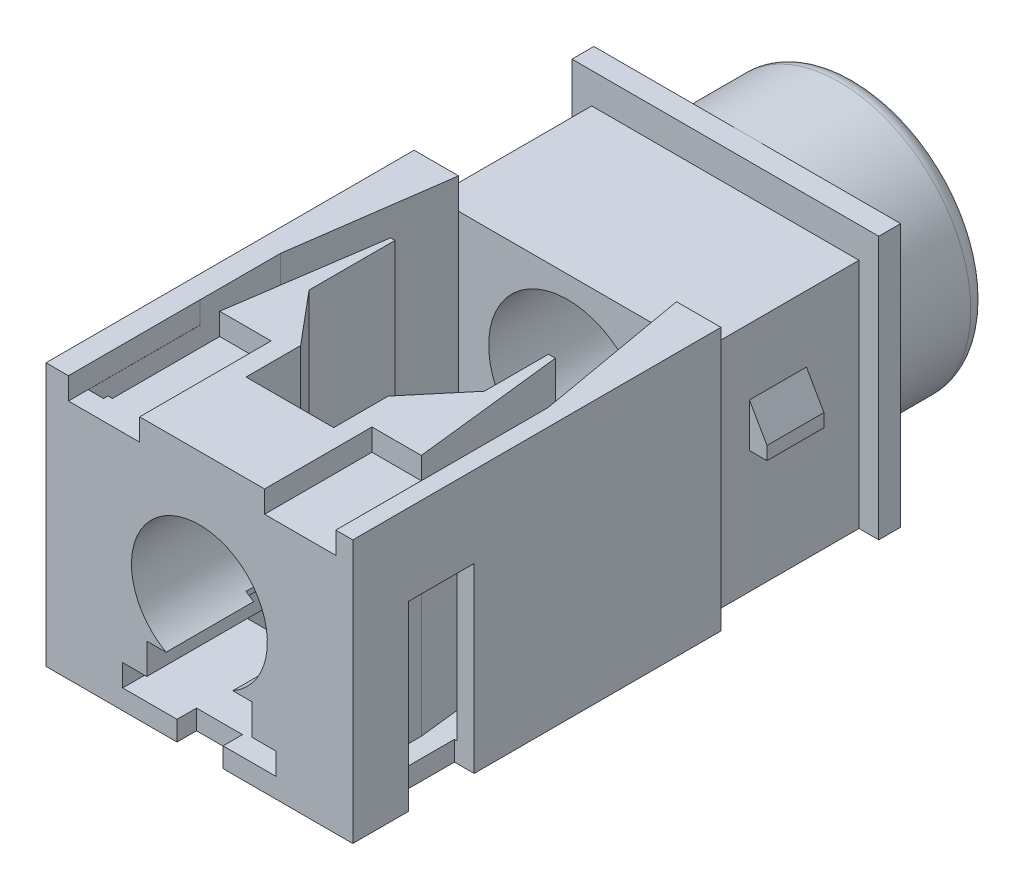
SolidWorks part; units mm, degrees
ref_plane "Front Plane" through (0, 0, 0) normal (0, 0, 1) x (1, 0, 0)
ref_plane "Top Plane" through (0, 0, 0) normal (0, 1, 0) x (1, 0, 0)
ref_plane "Right Plane" through (0, 0, 0) normal (1, 0, 0) x (0, 0, -1)
sketch "Szkic1" plane through (0, 0, 0) normal (0, 0, 1) x (1, 0, 0)
  circle A0 centre (0, 0) radius 3
  circle A1 centre (0, 0) radius 1.8
  dimension "D1" = 6
  dimension "D2" = 3.6
extrude "Dodanie-wyciągnięcie1" add sketch "Szkic1" along normal blind 2.5
sketch "Szkic2" plane through (0, 0, 2.5) normal (0, 0, 1) x (1, 0, 0)
  line L5 (3.5, -3) -> (-3.5, -3)
  line L6 (3.5, -3) -> (3.5, 3)
  line L7 (3.5, 3) -> (-3.5, 3)
  line L8 (-3.5, -3) -> (-3.5, 3)
  line L9 (3.5, -3) -> (-3.5, 3) construction
  line L10 (3.5, 3) -> (-3.5, -3) construction
  circle A2 centre (0, 0) radius 1.8 construction
  circle A3 centre (0, 0) radius 1.8
  dimension "D1" = 6
  dimension "D2" = 7
extrude "Dodanie-wyciągnięcie2" add sketch "Szkic2" along normal blind 0.5
fillet "Zaokrąglenie1" radius 0.4 1 edges at (3, 0, 0)
chamfer "Sfazowanie1" distance 0.4 angle 45 1 edges at (1.8, 0, 0)
sketch "Szkic3" plane through (0, 0, 3) normal (0, 0, 1) x (1, 0, 0)
  line L0 (0, 2.3) -> (0, -3) construction
  line L1 (-3.5, -3) -> (3.5, -3) construction
  line L2 (-3.05, 2.3) -> (3.05, 2.3)
  line L3 (-3.05, 2.3) -> (-3.05, -3)
  line L4 (-3.05, -3) -> (3.05, -3)
  line L5 (3.05, -3) -> (3.05, 2.3)
  line L6 (3.5, 3) -> (-3.5, 3) construction
  circle A0 centre (0, 0) radius 1.8 construction
  circle A1 centre (0, 0) radius 1.8
  dimension "D1" = 0.7
  dimension "D2" = 6.1
extrude "Dodanie-wyciągnięcie3" add sketch "Szkic3" along normal blind 3.6
ref_plane "Płaszczyzna1" through (0, 0, 4.3) normal (0, 0, 1) x (1, 0, 0)
sketch "Szkic4" plane through (0, 0, 4.3) normal (0, 0, 1) x (1, 0, 0)
  line L0 (3.05, 0.7904) -> (3.05, 3) construction
  line L1 (3.05, 3) -> (3.5, 3) construction
  line L2 (3.05, 0.7904) -> (3.05, -0.2096)
  line L3 (3.05, -0.2096) -> (3.45, -0.2096)
  line L4 (3.45, -0.2096) -> (3.45, 0.0904)
  line L5 (3.45, 0.0904) -> (3.05, 0.7904)
extrude "Dodanie-wyciągnięcie4" add sketch "Szkic4" along normal blind 1.3 from offset 0.1 separate body offset against normal yes
mirror "Lustro1" about plane through (0, 0, 0) normal (1, 0, 0) of bodies 104
sketch "Szkic5" plane through (0, 0, 6.6) normal (0, 0, 1) x (1, 0, 0)
  line L0 (-3.5, -3) -> (3.5, -3)
  line L1 (-3.5, -3) -> (-3.5, 3)
  line L2 (-3.5, 3) -> (-3.5, -3) construction
  line L3 (-3.5, 3) -> (3.5, 3)
  line L4 (3.5, 3) -> (3.5, -3)
  circle A0 centre (0, 0) radius 1.55
  dimension "D2" = 3.1
  dimension "D1" = 6
extrude "Dodanie-wyciągnięcie5" add sketch "Szkic5" along normal blind 8.4 separate body
sketch "Szkic7" plane through (0, -3, 0) normal (0, -1, 0) x (1, 0, 0)
  line L0 (1.75, 11.0559) -> (1.75, 12.2059)
  line L1 (0.9, 11.0559) -> (1.75, 11.0559)
  line L2 (0.9, 12.2059) -> (0.9, 11.0559)
  line L3 (1.75, 12.2059) -> (0.9, 12.2059)
  line L4 (-1.75, 11.0559) -> (-0.9, 11.0559)
  line L5 (-1.75, 12.2059) -> (-1.75, 11.0559)
  line L6 (-0.9, 11.0559) -> (-0.9, 12.2059)
  line L7 (-0.9, 12.2059) -> (-1.75, 12.2059)
  line L8 (0.54, 14.5559) -> (0.54, 15.0309)
  line L9 (-0.51, 14.5559) -> (0.54, 14.5559)
  line L10 (-0.51, 15.0309) -> (-0.51, 14.5559)
  line L11 (3.05, 12.2309) -> (3.05, 13.5309)
  line L12 (3.5, 12.2309) -> (3.05, 12.2309)
  line L13 (3.5, 12.2309) -> (3.5, 13.7309)
  line L14 (3.05, 13.7309) -> (3.5, 13.7309)
  line L15 (3.05, 13.7309) -> (3.05, 14.5809)
  line L16 (2.7, 14.5809) -> (3.05, 14.5809)
  line L17 (2.7, 14.5809) -> (2.7, 13.5309)
  line L18 (3.05, 13.5309) -> (2.7, 13.5309)
  line L19 (-3.05, 13.7309) -> (-3.5, 13.7309)
  line L20 (-3.5, 13.7309) -> (-3.5, 12.2309)
  line L21 (-3.05, 12.2309) -> (-3.5, 12.2309)
  line L22 (-3.05, 13.5309) -> (-3.05, 12.2309)
  line L23 (-2.7, 13.5309) -> (-3.05, 13.5309)
  line L24 (-3.05, 14.5809) -> (-3.05, 13.7309)
  line L25 (-3.05, 14.5809) -> (-2.7, 14.5809)
  line L26 (-2.7, 13.5309) -> (-2.7, 14.5809)
  line L27 (0.015, 15.0309) -> (0.0296, 18.44) construction
  line L28 (-0.51, 15.0309) -> (0.54, 15.0309)
  circle A0 centre (0, 4.5309) radius 0.475
  circle A1 centre (0, 11.5309) radius 0.475
sketch "Szkic8" plane through (0, -3, 0) normal (0, -1, 0) x (1, 0, 0)
  circle A0 centre (0, 11.5309) radius 0.475 construction
  circle A1 centre (0, 4.5309) radius 0.475 construction
  circle A2 centre (0, 11.5309) radius 0.475
  circle A3 centre (0, 4.5309) radius 0.475
extrude "Dodanie-wyciągnięcie6" add sketch "Szkic8" along normal blind 0.8 separate body
fillet "Zaokrąglenie2" radius 0.2 1 edges at (0.475, -3.8, 4.5309)
fillet "Zaokrąglenie3" radius 0.2 1 edges at (0.475, -3.8, 11.5309)
sketch "Szkic9" plane through (0, -3, 0) normal (0, -1, 0) x (1, 0, 0)
  line L0 (0.9, 11.0559) -> (1.75, 11.0559) construction
  line L1 (1.75, 11.0559) -> (1.75, 12.2059) construction
  line L2 (1.75, 12.2059) -> (0.9, 12.2059) construction
  line L3 (0.9, 12.2059) -> (0.9, 11.0559) construction
  line L4 (-0.9, 12.2059) -> (-1.75, 12.2059) construction
  line L5 (-1.75, 12.2059) -> (-1.75, 11.0559) construction
  line L6 (-1.75, 11.0559) -> (-0.9, 11.0559) construction
  line L7 (-0.9, 11.0559) -> (-0.9, 12.2059) construction
  line L8 (0.9, 11.0559) -> (1.75, 11.0559)
  line L9 (1.75, 11.0559) -> (1.75, 12.2059)
  line L10 (1.75, 12.2059) -> (0.9, 12.2059)
  line L11 (0.9, 12.2059) -> (0.9, 11.0559)
  line L12 (-0.9, 12.2059) -> (-1.75, 12.2059)
  line L13 (-1.75, 12.2059) -> (-1.75, 11.0559)
  line L14 (-1.75, 11.0559) -> (-0.9, 11.0559)
  line L15 (-0.9, 11.0559) -> (-0.9, 12.2059)
extrude "Wytnij-wyciągnięcie1" cut sketch "Szkic9" against normal blind 0.95
sketch "Szkic10" plane through (0, -3, 0) normal (0, -1, 0) x (1, 0, 0)
  line L0 (0.54, 14.5559) -> (0.54, 15.0309) construction
  line L1 (-0.51, 14.5559) -> (0.54, 14.5559) construction
  line L2 (-0.51, 15.0309) -> (-0.51, 14.5559) construction
  line L3 (-0.51, 15.0309) -> (0.54, 15.0309) construction
  line L4 (0.54, 14.5559) -> (0.54, 15.0309)
  line L5 (-0.51, 14.5559) -> (0.54, 14.5559)
  line L6 (-0.51, 15.0309) -> (-0.51, 14.5559)
  line L7 (-0.51, 15.0309) -> (0.54, 15.0309)
extrude "Wytnij-wyciągnięcie2" cut sketch "Szkic10" against normal blind 2
sketch "Szkic11" plane through (0, -3, 0) normal (0, -1, 0) x (1, 0, 0)
  line L0 (3.05, 13.5309) -> (2.7, 13.5309) construction
  line L1 (2.7, 14.5809) -> (2.7, 13.5309) construction
  line L2 (2.7, 14.5809) -> (3.05, 14.5809) construction
  line L3 (3.05, 13.7309) -> (3.05, 14.5809) construction
  line L4 (3.05, 13.7309) -> (3.5, 13.7309) construction
  line L5 (3.5, 12.2309) -> (3.5, 13.7309) construction
  line L6 (3.5, 12.2309) -> (3.05, 12.2309) construction
  line L7 (3.05, 12.2309) -> (3.05, 13.5309) construction
  line L8 (-3.05, 13.5309) -> (-3.05, 12.2309) construction
  line L9 (-2.7, 13.5309) -> (-3.05, 13.5309) construction
  line L10 (-2.7, 13.5309) -> (-2.7, 14.5809) construction
  line L11 (-3.05, 14.5809) -> (-2.7, 14.5809) construction
  line L12 (-3.05, 14.5809) -> (-3.05, 13.7309) construction
  line L13 (-3.05, 13.7309) -> (-3.5, 13.7309) construction
  line L14 (-3.5, 13.7309) -> (-3.5, 12.2309) construction
  line L15 (-3.05, 12.2309) -> (-3.5, 12.2309) construction
  line L16 (3.05, 13.5309) -> (2.7, 13.5309)
  line L17 (2.7, 14.5809) -> (2.7, 13.5309)
  line L18 (2.7, 14.5809) -> (3.05, 14.5809)
  line L19 (3.05, 13.7309) -> (3.05, 14.5809)
  line L20 (3.05, 13.7309) -> (3.5, 13.7309)
  line L21 (3.5, 12.2309) -> (3.5, 13.7309)
  line L22 (3.5, 12.2309) -> (3.05, 12.2309)
  line L23 (3.05, 12.2309) -> (3.05, 13.5309)
  line L24 (-3.05, 13.5309) -> (-3.05, 12.2309)
  line L25 (-2.7, 13.5309) -> (-3.05, 13.5309)
  line L26 (-2.7, 13.5309) -> (-2.7, 14.5809)
  line L27 (-3.05, 14.5809) -> (-2.7, 14.5809)
  line L28 (-3.05, 14.5809) -> (-3.05, 13.7309)
  line L29 (-3.05, 13.7309) -> (-3.5, 13.7309)
  line L30 (-3.5, 13.7309) -> (-3.5, 12.2309)
  line L31 (-3.05, 12.2309) -> (-3.5, 12.2309)
extrude "Wytnij-wyciągnięcie3" cut sketch "Szkic11" against normal blind 4.15
sketch "Szkic12" plane through (0, 0, 15) normal (0, 0, 1) x (1, 0, 0)
  line L0 (1.75, -2.05) -> (1.75, -2.55)
  line L1 (-1.75, -2.55) -> (-1.75, -2.05)
  line L2 (1.75, -2.55) -> (0.54, -2.55)
  line L3 (-0.51, -2.55) -> (-1.75, -2.55)
  line L4 (-1.2, -2.05) -> (-1.75, -2.05)
  line L5 (1.75, -2.05) -> (1.2, -2.05)
  line L6 (1.2, -1.35) -> (1.2, -2.05)
  line L7 (1.2, -1.35) -> (0.7616, -1.35)
  line L8 (-0.7616, -1.35) -> (-1.2, -1.35)
  line L9 (-1.2, -2.05) -> (-1.2, -1.35)
  line L10 (0, 1.55) -> (0, 3) construction
  line L11 (0.54, -2.55) -> (-0.51, -2.55)
  arc A0 (0.7616, -1.35) -> (-0.7616, -1.35) centre (0, 0) ccw
extrude "Wytnij-wyciągnięcie4" cut sketch "Szkic12" against normal up to surface (8.4 mm away) up to face at (0, 0, 6.6)
sketch "Szkic13" plane through (0, 3, 0) normal (0, 1, 0) x (1, 0, 0)
  line L0 (-2.9863, -10.1577) -> (-2.9863, -14.55)
  line L1 (-2.4863, -6.6) -> (-2.9863, -10.1577)
  line L2 (-2.4863, -6.6) -> (2.4863, -6.6)
  line L3 (3.1137, -14.55) -> (3.1137, -10.1577)
  line L4 (2.4863, -6.6) -> (3.1137, -10.1577)
  line L5 (-2.5363, -14.45) -> (-2.5363, -12)
  line L6 (-2.5363, -12) -> (-1.3613, -12)
  line L7 (-1.3613, -12) -> (-1.3613, -15)
  line L8 (-1.3613, -15) -> (1.4887, -15)
  line L9 (1.4887, -15) -> (1.4887, -12.55)
  line L10 (1.4887, -12.55) -> (2.6125, -12.55)
  line L11 (2.6125, -12.55) -> (2.2205, -9.1)
  line L12 (2.2205, -9.1) -> (2.0637, -9.1)
  line L13 (2.0637, -9.1) -> (2.0637, -10.5616)
  line L14 (2.0637, -10.5616) -> (1.0637, -11.7534)
  line L15 (1.0637, -11.7534) -> (1.0637, -13)
  line L16 (1.0637, -13) -> (-0.9363, -13)
  line L17 (-0.9363, -13) -> (-0.9363, -11.7534)
  line L18 (-0.9363, -11.7534) -> (-1.9363, -10.5616)
  line L19 (-1.9363, -10.5616) -> (-1.9363, -8.6)
  line L20 (-1.9363, -8.6) -> (-2.0363, -8.6)
  line L21 (-2.0363, -8.6) -> (-2.5363, -12)
  line L22 (-2.6363, -14.45) -> (-2.5363, -14.45)
  line L23 (-2.6363, -14.45) -> (-2.6363, -14.55)
  line L24 (-2.9863, -14.55) -> (-2.6363, -14.55)
  line L25 (2.6125, -12.55) -> (2.6125, -14.45)
  line L26 (2.6125, -14.45) -> (2.7637, -14.45)
  line L27 (2.7637, -14.45) -> (2.7637, -14.55)
  line L28 (3.1137, -14.55) -> (2.7637, -14.55)
  line L29 (0, -6.6) -> (0, -0.9682) construction
  line M17 (3.5, -6.6) -> (-3.5, -6.6)
extrude "Wytnij-wyciągnięcie5" cut sketch "Szkic13" against normal up to surface (5.55 mm away) contours L28 L3 L4 L2 L1 L0 L24 L23 L22 L5 L21 L20 L19 L18 L17 L16 L15 L14 L13 L12 L11 L25 L26 L27 M17 region at (0.0749, 3, 9.687) up to face at (0.0038, -2.55, 12.21)
sketch "Szkic14" plane through (0, 3, 0) normal (0, 1, 0) x (1, 0, 0)
  line L0 (0, -15) -> (0, -17.8683) construction
  line L1 (3.5, -15) -> (-3.5, -15) construction
  line L2 (3.1118, -15) -> (1.4868, -15)
  line L3 (1.4868, -15) -> (1.4868, -12.55)
  line L4 (1.4868, -12.55) -> (3.1118, -12.55)
  line L5 (3.1118, -12.55) -> (3.1118, -15)
  line L6 (-1.3632, -15) -> (-2.9882, -15)
  line L7 (-2.9882, -15) -> (-2.9882, -12)
  line L8 (-2.9882, -12) -> (-1.3632, -12)
  line L9 (-1.3632, -12) -> (-1.3632, -15)
  line L10 (-2.9882, -15) -> (-3.4382, -15) construction
extrude "Wytnij-wyciągnięcie6" cut sketch "Szkic14" against normal blind 0.5
